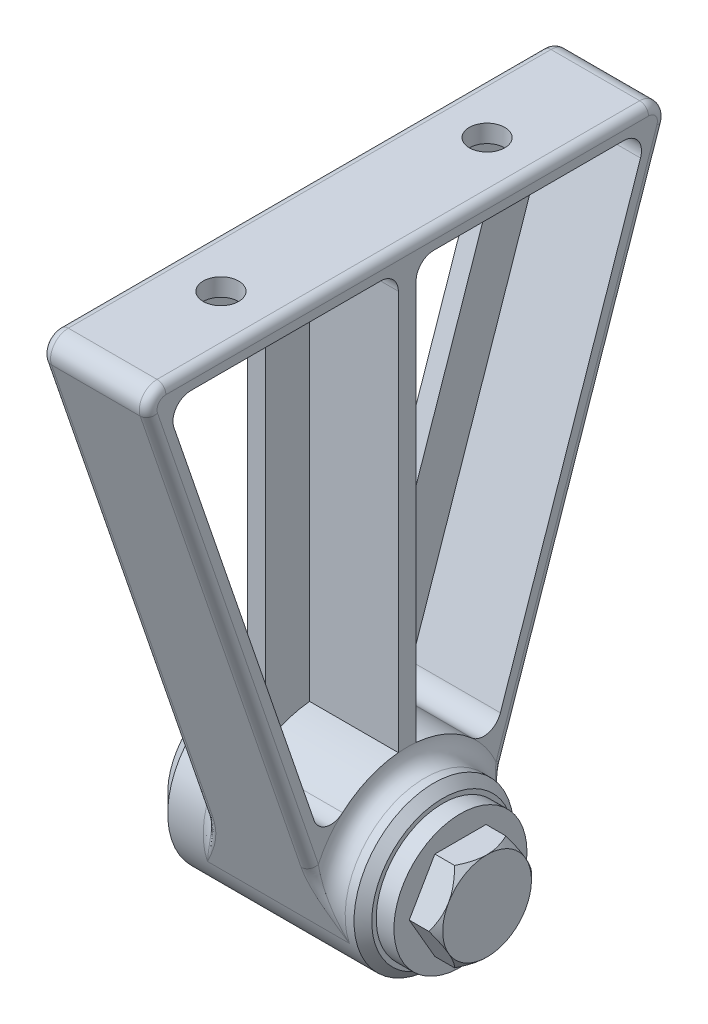
SolidWorks part; units mm, degrees
ref_plane "Front Plane" through (0, 0, 0) normal (0, 0, 1) x (1, 0, 0)
ref_plane "Top Plane" through (0, 0, 0) normal (0, 1, 0) x (1, 0, 0)
ref_plane "Right Plane" through (0, 0, 0) normal (1, 0, 0) x (0, 0, -1)
sketch "Sketch1" plane through (0, 0, 0) normal (1, 0, 0) x (0, 0, -1)
  circle A0 centre (0, 0) radius 30
  circle A1 centre (0, 0) radius 45
  dimension "D1" = 60
  dimension "D2" = 90
extrude "Boss-Extrude1" add sketch "Sketch1" along normal blind 120
sketch "Sketch2" plane through (120, 0, 0) normal (1, 0, 0) x (0, 0, -1)
  circle A0 centre (0, 0) radius 37.5
  dimension "D1" = 75
extrude "Boss-Extrude2" add sketch "Sketch2" along normal blind 10
sketch "Sketch3" plane through (130, 0, 0) normal (1, 0, 0) x (0, 0, -1)
  line L1 (28.8675, 0) -> (14.4338, 25)
  line L2 (14.4338, 25) -> (-14.4338, 25)
  line L3 (-14.4338, 25) -> (-28.8675, 0)
  line L4 (-28.8675, 0) -> (-14.4338, -25)
  line L5 (-14.4338, -25) -> (14.4338, -25)
  line L6 (14.4338, -25) -> (28.8675, 0)
  circle A0 centre (0, 0) radius 25 construction
  dimension "D1" = 50
extrude "Boss-Extrude3" add sketch "Sketch3" along normal blind 15
sketch "Sketch4" plane through (145, 0, 0) normal (1, 0, 0) x (0, 0, -1)
  line L0 (28.8675, 0) -> (14.4338, 25) construction
  circle A0 centre (0, 0) radius 25
extrude "Cut-Extrude2" cut sketch "Sketch4" against normal blind 10 draft 45 flip side to cut
chamfer "Chamfer1" distance 5 angle 45 1 edges at (120, 0, -30)
chamfer "Chamfer2" distance 5 angle 45 1 edges at (120, 0, -45)
chamfer "Chamfer3" distance 10 angle 45 1 edges at (0, 0, -45)
ref_plane "Plane1" through (40, 0, 0) normal (1, 0, 0) x (0, 0, -1)
sketch "Sketch5" plane through (40, 0, 0) normal (1, 0, 0) x (0, 0, -1)
  line L0 (-150, 300) -> (150, 300)
  line L1 (0, 0) -> (0, 476.4045) construction
  line L2 (42.5853, -14.5427) -> (150, 300)
  line L3 (-42.5853, -14.5427) -> (-150, 300)
  circle A0 centre (0, 0) radius 45
  circle A2 centre (0, 0) radius 45 construction
  point P5 (0, 300)
  dimension "D1" = 300
  dimension "D2" = 150
extrude "Boss-Extrude4" add sketch "Sketch5" along normal blind 10 contours L1 A0 L2 L0 | A0 L1 L0 L3 region at (40, 184.7398, 55.7797) region at (40, 184.7398, -55.7797)
sketch "Sketch6" plane through (50, 0, 0) normal (1, 0, 0) x (0, 0, -1)
  line L0 (46.8329, 28.8389) -> (136.018, 290)
  line L1 (136.018, 290) -> (-136.018, 290)
  line L2 (-136.018, 290) -> (-46.8329, 28.8389)
  line L3 (150, 300) -> (-150, 300)
  line L4 (-150, 300) -> (-42.5853, -14.5427)
  line L5 (42.5853, -14.5427) -> (150, 300)
  line L6 (150, 300) -> (-150, 300)
  line L7 (-150, 300) -> (-42.5853, -14.5427)
  line L8 (42.5853, -14.5427) -> (150, 300)
  arc A0 (46.8329, 28.8389) -> (-46.8329, 28.8389) centre (0, 0) ccw
  arc A1 (42.5853, -14.5427) -> (-42.5853, -14.5427) centre (0, 0) ccw
  arc A2 (42.5853, -14.5427) -> (-42.5853, -14.5427) centre (0, 0) ccw
  dimension "D1" = 0
  dimension "D2" = 10
extrude "Boss-Extrude5" add sketch "Sketch6" along normal blind 50
sketch "Sketch7" plane through (100, 0, 0) normal (1, 0, 0) x (0, 0, -1)
  line L0 (0, 55) -> (0, 290)
  line L1 (136.018, 290) -> (-136.018, 290) construction
  arc A0 (46.8329, 28.8389) -> (-46.8329, 28.8389) centre (0, 0) ccw construction
rib "Rib1" sketch "Sketch7" sketch "Sketch7" thickness 10 extrusion direction normal to sketch draft on no parameters "D1"=10
fillet "Fillet3" radius 10 8 edges at (75, 28.8389, -46.8329) (75, 28.8389, 46.8329) (75, 290, 5) (75, 290, -5) (70, 300, -150) (75, 290, -136.018) (70, 300, 150) (75, 290, 136.018)
fillet "Fillet4" radius 10 2 edges at (40, 45, 0) (100, 45, 0)
sketch "Sketch8" plane through (50, 0, 0) normal (1, 0, 0) x (0, 0, -1)
  line L6 (35.1143, 71.8818) -> (101.0631, 265)
  line L7 (101.0631, 265) -> (30, 265)
  line L8 (30, 265) -> (30, 74.162)
  line L9 (35.1143, 71.8818) -> (101.0631, 265)
  line L10 (101.0631, 265) -> (30, 265)
  line L11 (30, 265) -> (30, 74.162)
  line L15 (-101.0631, 265) -> (-35.1143, 71.8818)
  line L16 (-30, 74.162) -> (-30, 265)
  line L17 (-30, 265) -> (-101.0631, 265)
  line L18 (-101.0631, 265) -> (-35.1143, 71.8818)
  line L19 (-30, 74.162) -> (-30, 265)
  line L20 (-30, 265) -> (-101.0631, 265)
  arc A8 (35.1143, 71.8818) -> (30, 74.162) centre (0, 0) ccw
  arc A9 (35.1143, 71.8818) -> (30, 74.162) centre (0, 0) ccw
  arc A14 (-30, 74.162) -> (-35.1143, 71.8818) centre (0, 0) ccw
  arc A15 (-30, 74.162) -> (-35.1143, 71.8818) centre (0, 0) ccw
  dimension "D1" = 25
  dimension "D2" = 25
extrude "Cut-Extrude3" cut sketch "Sketch8" against normal blind 50
sketch "Sketch9" plane through (0, 300, 0) normal (0, 1, 0) x (1, 0, 0)
  line L0 (0, 0) -> (145, 0) construction
  line L2 (40, 35.1143) -> (40, 101.0631) construction
  circle A0 centre (70, 75) radius 10
  circle A1 centre (70, -75) radius 10
  point P10 (40, 68.0887)
  dimension "D1" = 20
  dimension "D2" = 30
  dimension "D3" = 75
extrude "Cut-Extrude4" cut sketch "Sketch9" against normal blind 50
fillet "Fillet5" radius 5 7 edges at (37.6438, 2.7091, 48.4767) (40, 151.0758, 99.1432) (40, 295.8173, 144.1518) (37.6438, 2.7091, -48.4767) (40, 151.0758, -99.1432) (40, 295.8173, -144.1518) (40, 300, 0)
fillet "Fillet6" radius 5 7 edges at (102.3562, 2.7091, -48.4767) (100, 151.0758, -99.1432) (100, 295.8173, -144.1518) (102.3562, 2.7091, 48.4767) (100, 151.0758, 99.1432) (100, 295.8173, 144.1518) (100, 300, 0)
scale "Scale1" scale about centroid uniform scaling yes scale factor 0.25
